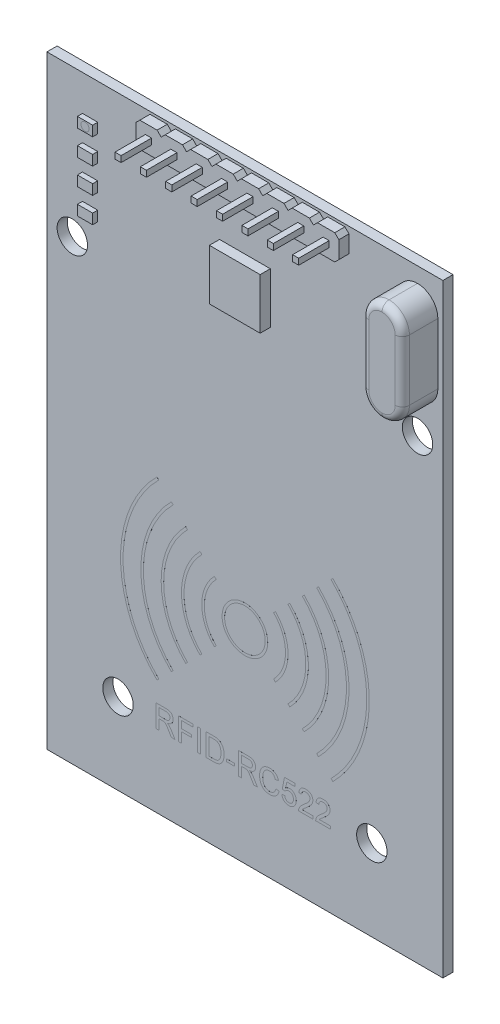
SolidWorks part; units mm, degrees
ref_plane "Спереди" through (0, 0, 0) normal (0, 0, 1) x (1, 0, 0)
ref_plane "Сверху" through (0, 0, 0) normal (0, 1, 0) x (1, 0, 0)
ref_plane "Справа" through (0, 0, 0) normal (1, 0, 0) x (0, 0, -1)
sketch "Эскиз1" plane through (0, 0, 0) normal (0, 0, 1) x (1, 0, 0)
  line L1 (19.5, -29.75) -> (-19.5, -29.75)
  line L2 (19.5, -29.75) -> (19.5, 29.75)
  line L3 (19.5, 29.75) -> (-19.5, 29.75)
  line L4 (-19.5, -29.75) -> (-19.5, 29.75)
  line L5 (19.5, -29.75) -> (-19.5, 29.75) construction
  line L6 (19.5, 29.75) -> (-19.5, -29.75) construction
  point P0 (0, 0)
  dimension "D1" = 39
  dimension "D2" = 59.5
extrude "Бобышка-Вытянуть1" add sketch "Эскиз1" along normal blind 1
sketch "Эскиз2" plane through (0, 0, 1) normal (0, 0, 1) x (1, 0, 0)
  line L1 (12.5, -21.75) -> (-12.5, -21.75) construction
  line L3 (17, 15.25) -> (-17, 15.25) construction
  line L5 (-19.5, -29.75) -> (19.5, -29.75) construction
  circle A0 centre (17, 15.25) radius 1.5
  circle A1 centre (-17, 15.25) radius 1.5
  circle A2 centre (-12.5, -21.75) radius 1.5
  circle A3 centre (12.5, -21.75) radius 1.5
  point P0 (0, -8.2129)
  point P5 (0, 15.25)
  point P7 (0, -21.75)
  dimension "D5" = 3
  dimension "D2" = 37
  dimension "D1" = 34
  dimension "D3" = 8
  dimension "D4" = 25
extrude "Вырез-Вытянуть1" cut sketch "Эскиз2" against normal through all
sketch "Эскиз4" plane through (0, 0, 0) normal (0, 0, -1) x (-1, 0, 0)
  line L1 (-19.5, 29.75) -> (19.5, 29.75) construction
  line L2 (-19.5, -29.75) -> (-19.5, 29.75) construction
  circle A0 centre (-9, 28.25) radius 0.45
  dimension "D1" = 0.9
  dimension "D2" = 10.5
  dimension "D3" = 1.5
extrude "Вырез-Вытянуть2" cut sketch "Эскиз4" against normal through all
pattern_linear "Линейный массив1" count 8 spacing 2.5 along (-1, 0, 0) of "Вырез-Вытянуть2"
sketch "Эскиз6" plane through (0, 0, 1) normal (0, 0, 1) x (1, 0, 0)
  text T0 "RFID-RC522" font "Arial" height 2.2
extrude "Бобышка-Вытянуть3" add sketch "Эскиз6" along normal blind 0.001
sketch "Эскиз7" plane through (0, 0, 1) normal (0, 0, 1) x (1, 0, 0)
  line L0 (19.5, 29.75) -> (-19.5, 29.75) construction
  line L1 (2.5, 17.25) -> (-2.5, 17.25)
  line L2 (2.5, 17.25) -> (2.5, 22.25)
  line L3 (2.5, 22.25) -> (-2.5, 22.25)
  line L4 (-2.5, 17.25) -> (-2.5, 22.25)
  line L5 (2.5, 17.25) -> (-2.5, 22.25) construction
  line L6 (2.5, 22.25) -> (-2.5, 17.25) construction
  point P0 (0, 19.75)
  dimension "D1" = 5
  dimension "D2" = 7.5
extrude "Бобышка-Вытянуть4" add sketch "Эскиз7" along normal blind 1
sketch "Эскиз8" plane through (0, 0, 1) normal (0, 0, 1) x (1, 0, 0)
  line L0 (19.5, -29.75) -> (19.5, 29.75) construction
  line L1 (19, 18.25) -> (15, 18.25)
  line L2 (19, 18.25) -> (19, 28.25)
  line L3 (19, 28.25) -> (15, 28.25)
  line L4 (15, 18.25) -> (15, 28.25)
  line L5 (19, 18.25) -> (15, 28.25) construction
  line L6 (19, 28.25) -> (15, 18.25) construction
  circle A0 centre (17, 15.25) radius 1.5 construction
  point P0 (17, 23.25)
  dimension "D1" = 10
  dimension "D2" = 4
  dimension "D3" = 0.5
  dimension "D4" = 3
extrude "Бобышка-Вытянуть5" add sketch "Эскиз8" along normal blind 3.5
sketch "Эскиз9" plane through (0, 0, 1) normal (0, 0, 1) x (1, 0, 0)
  line L0 (-19.5, -29.75) -> (19.5, -29.75) construction
  circle A0 centre (0, -9.75) radius 2
  arc A1 (-2.8284, -6.9216) -> (-2.8284, -12.5784) centre (0, -9.75) ccw
  arc A2 (-4.2426, -5.5074) -> (-4.2426, -13.9926) centre (0, -9.75) ccw
  arc A3 (-5.6569, -4.0931) -> (-5.6569, -15.4069) centre (0, -9.75) ccw
  arc A4 (-7.0711, -2.6789) -> (-7.0711, -16.8211) centre (0, -9.75) ccw
  arc A5 (-8.4853, -1.2647) -> (-8.4853, -18.2353) centre (0, -9.75) ccw
  arc A6 (2.8284, -12.5784) -> (2.8284, -6.9216) centre (0, -9.75) ccw
  arc A7 (4.2426, -13.9926) -> (4.2426, -5.5074) centre (0, -9.75) ccw
  arc A8 (5.6569, -15.4069) -> (5.6569, -4.0931) centre (0, -9.75) ccw
  arc A9 (7.0711, -16.8211) -> (7.0711, -2.6789) centre (0, -9.75) ccw
  arc A10 (8.4853, -18.2353) -> (8.4853, -1.2647) centre (0, -9.75) ccw
  dimension "D2" = 4
  dimension "D3" = 8
  dimension "D4" = 12
  dimension "D5" = 16
  dimension "D6" = 20
  dimension "D7" = 24
  dimension "D1" = 20
extrude "Вытянуть-Тонкостенный2" add sketch "Эскиз9" along normal blind 0.001 thin thin type one direction wall 0.25
sketch "Эскиз10" plane through (0, 0, 1) normal (0, 0, 1) x (1, 0, 0)
  line L0 (19.5, 29.75) -> (-19.5, 29.75) construction
  line L1 (-14.5, 25.25) -> (-16, 25.25)
  line L2 (-14.5, 25.25) -> (-14.5, 26.25)
  line L3 (-14.5, 26.25) -> (-16, 26.25)
  line L4 (-16, 25.25) -> (-16, 26.25)
  line L5 (-14.5, 25.25) -> (-16, 26.25) construction
  line L6 (-14.5, 26.25) -> (-16, 25.25) construction
  line L7 (-19.5, 29.75) -> (-19.5, -29.75) construction
  point P0 (-15.25, 25.75)
  dimension "D1" = 1.5
  dimension "D2" = 1
  dimension "D3" = 3.5
  dimension "D4" = 3.5
extrude "LED" add sketch "Эскиз10" along normal blind 0.5
sketch "Эскиз11" plane through (0, 0, 1.5) normal (0, 0, 1) x (1, 0, 0)
  line L0 (-14.5, 26.25) -> (-16, 26.25) construction
  line L1 (-16, 26.25) -> (-16, 25.25) construction
  circle A0 centre (-15.25, 25.75) radius 0.3996
  point P4 (-15.25, 26.25)
  point P7 (-16, 25.75)
  dimension "D1" = 0.7991
extrude "Бобышка-Вытянуть6" add sketch "Эскиз11" along normal blind 0.001
pattern_linear "Линейный массив2" count 4 spacing 2.5 along (0, -1, 0) of "LED"
fillet "Скругление1" radius 2 4 edges at (15, 18.25, 2.75) (19, 18.25, 2.75) (15, 28.25, 2.75) (19, 28.25, 2.75)
sketch "Эскиз12" plane through (0, 0, 1) normal (0, 0, 1) x (1, 0, 0)
  line L0 (-9.75, 27.4) -> (-9.35, 27)
  line L1 (-9.35, 29.5) -> (-7.65, 29.5)
  line L2 (-9.75, 29.1) -> (-9.75, 27.4)
  line L3 (-9.35, 27) -> (-7.65, 27)
  line L4 (-7.25, 29.1) -> (-7.25, 27.4)
  line L5 (-8.5, 27) -> (-8.5, 29.5) construction
  line L6 (-9.75, 28.25) -> (-7.25, 28.25) construction
  line L7 (-7.65, 27) -> (-7.25, 27.4)
  line L8 (-7.65, 29.5) -> (-7.25, 29.1)
  line L9 (-9.75, 29.1) -> (-9.35, 29.5)
  point P0 (-8.5, 28.25)
  point P1 (-7.25, 27)
  point P2 (-9.75, 29.5)
  point P3 (-9.75, 27)
  point P8 (-7.25, 29.5)
extrude "Бобышка-Вытянуть7" add sketch "Эскиз12" along normal blind 1
sketch "Эскиз14" plane through (0, 0, 0) normal (0, 0, -1) x (-1, 0, 0)
  line L0 (-6.2, 27.95) -> (-6.2, 28.55)
  line L1 (-8.7, 27.95) -> (-9.3, 27.95)
  line L2 (-8.7, 27.95) -> (-8.7, 28.55)
  line L3 (-8.7, 28.55) -> (-9.3, 28.55)
  line L4 (-9.3, 27.95) -> (-9.3, 28.55)
  line L5 (-9, 28.55) -> (-9, 27.95) construction
  line L6 (-8.7, 28.25) -> (-9.3, 28.25) construction
  line L7 (-6.2, 27.95) -> (-6.8, 27.95)
  line L8 (-6.8, 27.95) -> (-6.8, 28.55)
  line L9 (-6.2, 28.55) -> (-6.8, 28.55)
  line L10 (-3.7, 27.95) -> (-3.7, 28.55)
  line L11 (-3.7, 27.95) -> (-4.3, 27.95)
  line L12 (-4.3, 27.95) -> (-4.3, 28.55)
  line L13 (-3.7, 28.55) -> (-4.3, 28.55)
  line L14 (-1.2, 27.95) -> (-1.2, 28.55)
  line L15 (-1.2, 27.95) -> (-1.8, 27.95)
  line L16 (-1.8, 27.95) -> (-1.8, 28.55)
  line L17 (-1.2, 28.55) -> (-1.8, 28.55)
  line L18 (1.3, 27.95) -> (1.3, 28.55)
  line L19 (1.3, 27.95) -> (0.7, 27.95)
  line L20 (0.7, 27.95) -> (0.7, 28.55)
  line L21 (1.3, 28.55) -> (0.7, 28.55)
  line L22 (3.8, 27.95) -> (3.8, 28.55)
  line L23 (3.8, 27.95) -> (3.2, 27.95)
  line L24 (3.2, 27.95) -> (3.2, 28.55)
  line L25 (3.8, 28.55) -> (3.2, 28.55)
  line L26 (6.3, 27.95) -> (6.3, 28.55)
  line L27 (6.3, 27.95) -> (5.7, 27.95)
  line L28 (5.7, 27.95) -> (5.7, 28.55)
  line L29 (6.3, 28.55) -> (5.7, 28.55)
  line L30 (8.8, 27.95) -> (8.8, 28.55)
  line L31 (8.8, 27.95) -> (8.2, 27.95)
  line L32 (8.2, 27.95) -> (8.2, 28.55)
  line L33 (8.8, 28.55) -> (8.2, 28.55)
  point P0 (-9, 28.25)
  dimension "D1" = 0.6
  dimension "D2" = 8
extrude "Бобышка-Вытянуть8" add sketch "Эскиз14" along normal blind 1 and the other way blind 5
pattern_linear "Линейный массив3" count 8 spacing 2.5 along (1, 0, 0) of "Бобышка-Вытянуть7"
fillet "Скругление2" radius 0.7 6 edges at (15.5858, 27.6642, 4.5) (18.4142, 27.6642, 4.5) (19, 23.25, 4.5) (18.4142, 18.8358, 4.5) (15.5858, 18.8358, 4.5) (15, 23.25, 4.5)
